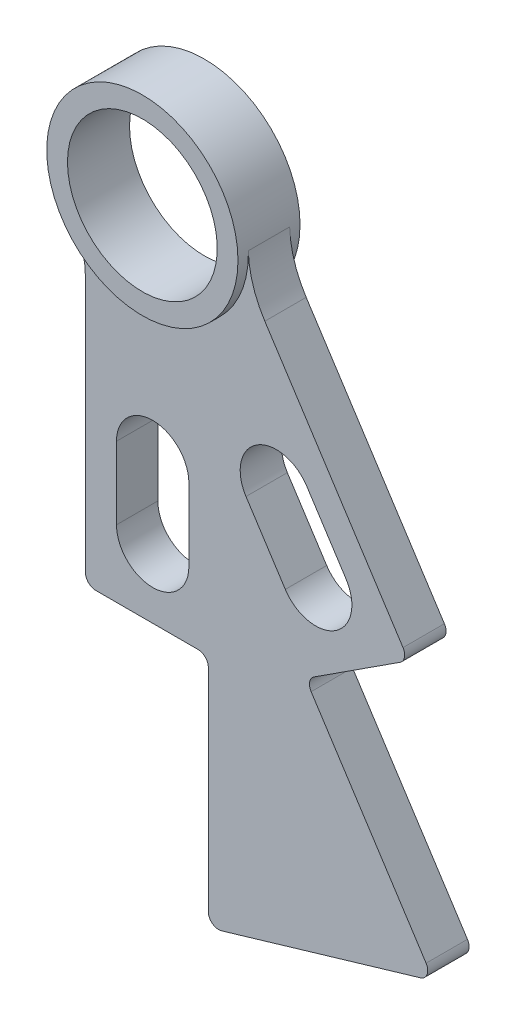
SolidWorks part; units mm, degrees
material "AISI 4130 Steel, annealed at 865C"
ref_plane "X-Y Datum" through (0, 0, 0) normal (0, 0, 1) x (1, 0, 0)
ref_plane "X-Z Datum" through (0, 0, 0) normal (0, 1, 0) x (1, 0, 0)
ref_plane "Y-Z Datum" through (0, 0, 0) normal (1, 0, 0) x (0, 0, -1)
sketch "Sketch1" plane through (0, 0, 0) normal (0, 0, 1) x (1, 0, 0)
  line L0 (0, -46.0556) -> (0, -34.9431) construction
  line L1 (-5.5563, -46.0556) -> (-5.5563, -34.9431)
  line L2 (5.5563, -46.0556) -> (5.5563, -34.9431)
  line L3 (25.0228, -38.6649) -> (18.9852, -29.3357) construction
  line L4 (20.3582, -41.6837) -> (14.3206, -32.3545)
  line L5 (29.6874, -35.6461) -> (23.6498, -26.3169)
  line L6 (-10.3187, -15.7343) -> (-10.3187, -56.3743)
  line L7 (-10.3187, -56.3743) -> (10.3188, -56.3743)
  line L10 (21.9663, -52.9341) -> (39.292, -41.7214)
  line L11 (39.292, -41.7214) -> (17.2116, -7.603)
  line L13 (8.5408, -92.5739) -> (43.1268, -82.3587)
  line L14 (0, -51.6118) -> (0, -56.3743) construction
  line L15 (28.0416, -43.3295) -> (30.6292, -47.3278) construction
  line L16 (26.6686, -30.9815) -> (30.6669, -28.3939) construction
  line L17 (-5.5563, -40.4993) -> (-10.3187, -40.4993) construction
  line L18 (-10.3187, -24.6243) -> (10.3187, -24.6243) construction
  line L19 (10.3187, -24.6243) -> (10.3188, -56.3743) construction
  line L20 (5.5563, -40.4993) -> (10.3188, -40.4993) construction
  line L21 (0, -29.3868) -> (0, -24.6243) construction
  line L22 (21.9663, -52.9341) -> (4.716, -26.2791) construction
  line L23 (4.716, -26.2791) -> (22.0417, -15.0664) construction
  line L24 (17.3394, -37.0191) -> (13.3411, -39.6066) construction
  line L25 (15.9664, -24.671) -> (13.3788, -20.6728) construction
  line L31 (8.5408, -56.3743) -> (8.5408, -92.5739)
  line L33 (23.459, -51.9681) -> (43.1268, -82.3587)
  line L34 (218.5438, -337.6911) -> (0, 0) construction
  line L35 (0, -404.7476) -> (0, 0) construction
  circle A0 centre (0, 0) radius 11.4954
  arc A1 (-5.5563, -46.0556) -> (5.5563, -46.0556) centre (0, -46.0556) ccw
  arc A2 (5.5563, -34.9431) -> (-5.5563, -34.9431) centre (0, -34.9431) ccw
  arc A3 (20.3582, -41.6837) -> (29.6874, -35.6461) centre (25.0228, -38.6649) ccw
  arc A4 (23.6498, -26.3169) -> (14.3206, -32.3545) centre (18.9852, -29.3357) ccw
  arc A5 (14.673, 0.4911) -> (-12.5852, -7.5598) centre (0, 0) ccw
  arc A6 (17.2116, -7.603) -> (14.673, 0.4911) centre (30.5391, 1.0221) cw
  arc A7 (-10.3187, -15.7343) -> (-12.5852, -7.5598) centre (-26.1937, -15.7343) ccw
  arc A14 (-12.5852, -7.5598) -> (14.673, 0.4911) centre (0, 0) ccw
  point P5 (0, -40.4993)
  point P11 (22.004, -34.0003)
  point P24 (30.6292, -47.3278)
  point P31 (0, -56.3743)
  point P37 (23.459, -51.9681)
  point P39 (28.0416, -43.3295)
  point P51 (8.5408, -56.3743)
  dimension "D1" = 22.9908
  dimension "D2" = 14.6812
  dimension "D8" = 15.875
  dimension "D9" = 1.778
  dimension "D3" = 1.778
  dimension "D4" = 4.7625
  dimension "D5" = 31.75
  dimension "D6" = 8.89
  dimension "D7" = 8.89
extrude "Boss-Extrude2" add sketch "Sketch1" along normal mid plane 9.525 contours A5 A14 A0 region at (-4.041, 13.6817, 0)
extrude "Boss-Extrude3" add sketch "Sketch1<4>" along normal mid plane 6.35 contours A14 A7 L6 L7 L10 L11 A6 A4 L5 A3 L4 A2 L2 A1 L1 region at (14.5286, -49.1899, 0)
sketch "Sketch1<4>" plane through (0, 0, 0) normal (0, 0, 1) x (1, 0, 0) same geometry as "Sketch1"
fillet "Fillet1" radius 1.5875 6 edges at (-10.3187, -56.3743, 0) (39.292, -41.7214, 0) (8.5408, -92.5739, 0) (43.1268, -82.3587, 0) (23.459, -51.9681, 0) (8.5408, -56.3743, 0)
sketch "Sketch2" plane through (0, 0, 4.7625) normal (0, 0, 1) x (1, 0, 0)
  point P0 (0, 0)
sketch "Sketch3" plane through (0, 0, -4.7625) normal (0, 0, -1) x (-1, 0, 0)
  point P0 (0, 0)
